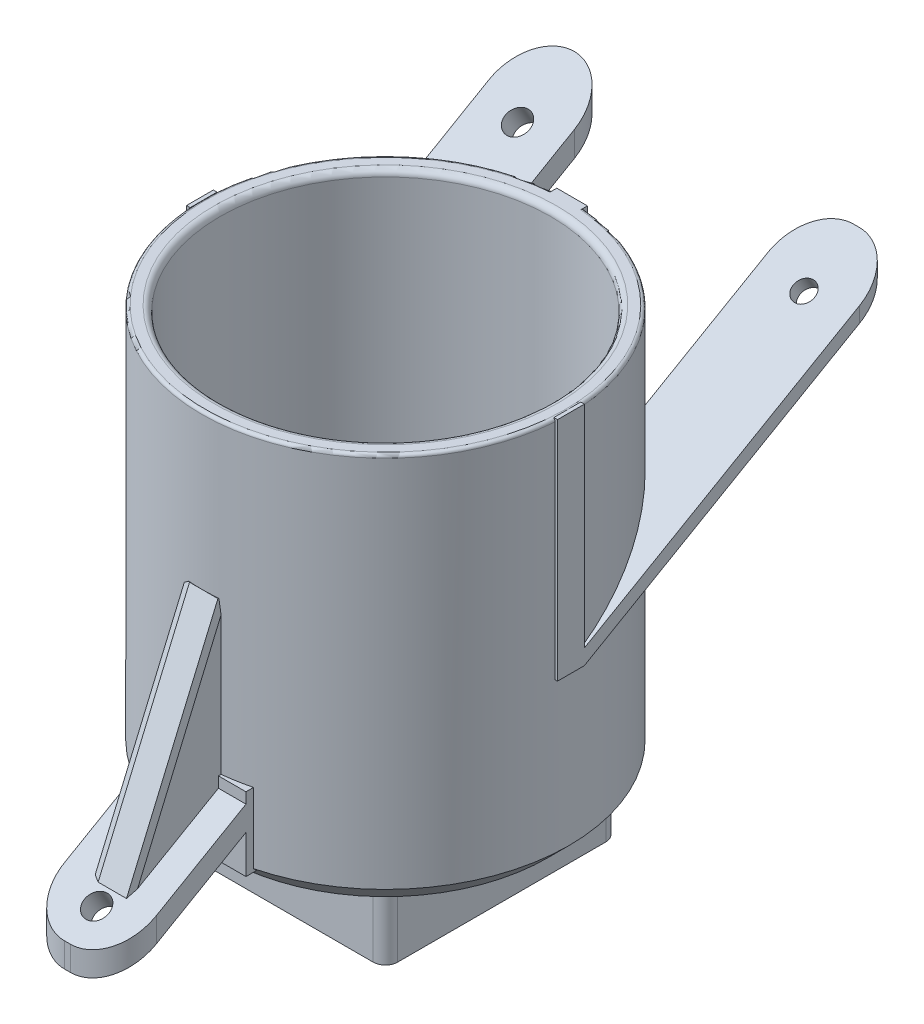
SolidWorks part; units mm, degrees
ref_plane "Alzado" through (0, 0, 0) normal (0, 0, 1) x (1, 0, 0)
ref_plane "Planta" through (0, 0, 0) normal (0, 1, 0) x (1, 0, 0)
ref_plane "Vista lateral" through (0, 0, 0) normal (1, 0, 0) x (0, 0, -1)
sketch "Croquis1" plane through (0, 0, 0) normal (0, 1, 0) x (1, 0, 0)
  circle A0 centre (0, 0) radius 16
  circle A1 centre (0, 0) radius 19
extrude "Saliente-Extruir1" add sketch "Croquis1" along normal blind 2.8
sketch "Croquis2" plane through (0, 0, 0) normal (0, -1, 0) x (-1, 0, 0)
  line L1 (16, 16) -> (-16, 16)
  line L2 (16, 16) -> (16, -16)
  line L3 (16, -16) -> (-16, -16)
  line L4 (-16, 16) -> (-16, -16)
  line L5 (16, 16) -> (-16, -16) construction
  line L6 (16, -16) -> (-16, 16) construction
  line L7 (19, 19) -> (-19, 19)
  line L8 (19, 19) -> (19, -19)
  line L9 (19, -19) -> (-19, -19)
  line L10 (-19, 19) -> (-19, -19)
  line L11 (19, 19) -> (-19, -19) construction
  line L12 (19, -19) -> (-19, 19) construction
  point P0 (0, 0)
  point P5 (0, 0)
extrude "Saliente-Extruir2" add sketch "Croquis2" along normal blind 10
sketch "Croquis3" plane through (0, 0, 0) normal (0, -1, 0) x (1, 0, 0)
  circle A1 centre (0, 0) radius 28
  circle A2 centre (0, 0) radius 16
extrude "Saliente-Extruir4" add sketch "Croquis3" against normal blind 3
sketch "Croquis4" plane through (0, 3, 0) normal (0, 1, 0) x (1, 0, 0)
  circle A2 centre (0, 0) radius 27
  circle A3 centre (0, 0) radius 30
extrude "Saliente-Extruir7" add sketch "Croquis4" along normal blind 63 and the other way up to surface other way up to face at (0, 0, -28)
chamfer "Chaflán2" distance 3.5 angle 45 1 edges at (0, 0, -30)
fillet "Redondeo5" radius 2 4 edges at (-19, -4.815, -19) (-19, -4.815, 19) (19, -4.815, 19) (19, -4.815, -19)
sketch "Croquis7" plane through (19, 0, 0) normal (1, 0, 0) x (0, 0, -1)
  line L1 (30, 66) -> (-30, 66) construction
  line L2 (0, 66) -> (0, 65)
  line L4 (-30, 65) -> (30, 65)
  line L5 (-30, 65) -> (-30, 66)
  line L6 (-30, 66) -> (30, 66)
  line L7 (30, 65) -> (30, 66)
  line L8 (-30, 65) -> (30, 66) construction
  line L9 (-30, 66) -> (30, 65) construction
  point P5 (0, 65.5)
extrude "Cortar-Extruir1" cut sketch "Croquis7" against normal through all and the other way through all contours L4 L7 L6 L2 | L6 L5 L4 L2
fillet "Redondeo6" radius 1 1 edges at (0, 65, -27)
fillet "Redondeo7" radius 0.5 1 edges at (0, 65, -30)
sketch "Croquis9" plane through (0, 65, 0) normal (0, 1, 0) x (1, 0, 0)
  line L0 (-2.5, 30) -> (-2.5, 30.5)
  line L3 (-2.5, 30) -> (-2.5, 29)
  line L4 (-2.5, 29) -> (0, 29)
  line L5 (0, 29) -> (2.5, 29)
  line L6 (2.5, 29) -> (2.5, 30)
  line L7 (-2.5, 30.5) -> (2.5, 30.5)
  line L8 (2.5, 30.5) -> (2.5, 30)
sketch "Croquis14" plane through (0, -10, 0) normal (0, -1, 0) x (1, 0, 0)
  line L5 (16.5, -16.5) -> (-16.5, -16.5)
  line L6 (16.5, -16.5) -> (16.5, 16.5)
  line L7 (16.5, 16.5) -> (-16.5, 16.5)
  line L8 (-16.5, -16.5) -> (-16.5, 16.5)
  line L9 (-16, 16) -> (16, 16)
  line L10 (-16, 16) -> (-16, -16)
  line L11 (-16, -16) -> (16, -16)
  line L12 (16, 16) -> (16, -16)
extrude "Cortar-Extruir2" cut sketch "Croquis14" against normal up to surface (10 mm away) up to face at (-11.7712, 0, 11.7712)
extrude "Saliente-Extruir8" add sketch "Croquis9" against normal blind 18
sketch "Croquis22" plane through (0, 65, 0) normal (0, 1, 0) x (1, 0, 0)
  line L1 (29.7, -2.194) -> (30.3, -2.194)
  line L2 (29.7, -2.194) -> (29.7, 2.194)
  line L3 (29.7, 2.194) -> (30.3, 2.194)
  line L4 (30.3, -2.194) -> (30.3, 2.194)
  line L5 (29.7, -2.194) -> (30.3, 2.194) construction
  line L6 (29.7, 2.194) -> (30.3, -2.194) construction
  line L7 (-30.3, -2.194) -> (-29.7, -2.194)
  line L8 (-30.3, -2.194) -> (-30.3, 2.194)
  line L9 (-30.3, 2.194) -> (-29.7, 2.194)
  line L10 (-29.7, -2.194) -> (-29.7, 2.194)
  line L11 (-30.3, -2.194) -> (-29.7, 2.194) construction
  line L12 (-30.3, 2.194) -> (-29.7, -2.194) construction
  arc A0 (-2.5, 29.8957) -> (2.5, 29.8957) centre (0, 0) ccw construction
  point P0 (30, 0)
  point P8 (-30, 0)
extrude "Saliente-Extruir9" add sketch "Croquis22" against normal blind 37
sketch "Croquis27" plane through (30.3, 0, 0) normal (1, 0, 0) x (0, 0, -1)
  line L0 (2.194, 28) -> (54.1555, 58)
  line L1 (2.194, 28) -> (2.194, 30.5)
  line L2 (2.194, 30.5) -> (54.1555, 60.5)
  line L3 (54.1555, 58) -> (54.1555, 60.5)
extrude "Saliente-Extruir10" add sketch "Croquis27" against normal blind 15
sketch "Croquis28" plane through (-30.3, 0, 0) normal (-1, 0, 0) x (0, 0, 1)
  line L0 (-2.194, 28) -> (-54.1555, 58)
  line L1 (-54.1555, 58) -> (-54.1555, 60.5)
  line L2 (-54.1555, 60.5) -> (-2.194, 30.5)
  line L3 (-2.194, 30.5) -> (-2.194, 28)
  line L4 (-2.194, 30.5) -> (-2.194, 32)
  line L5 (-2.194, 64.5) -> (-2.194, 28) construction
  line L6 (-2.194, 32) -> (-54.1555, 62.1174)
  line L7 (-54.1555, 62.1174) -> (-54.1555, 60.5)
  line M2 (-2.194, 65) -> (-2.194, 28)
sketch "Croquis31" plane through (0, 65, 0) normal (0, 1, 0) x (1, 0, 0)
  line L1 (-7.5, -30.2835) -> (7.5, -30.2835)
  line L2 (-7.5, -30.2835) -> (-7.5, -28.5835)
  line L3 (-7.5, -28.5835) -> (7.5, -28.5835)
  line L4 (7.5, -30.2835) -> (7.5, -28.5835)
  line L5 (-7.5, -30.2835) -> (7.5, -28.5835) construction
  line L6 (-7.5, -28.5835) -> (7.5, -30.2835) construction
  point P0 (0, -29.4335)
extrude "Saliente-Extruir13" add sketch "Croquis31" along normal blind 12 from offset 62 offset against normal yes
sketch "Croquis32" plane through (-7.5, 0, 0) normal (-1, 0, 0) x (0, 0, 1)
  line L2 (30.2835, 9.2491) -> (30.2835, 13.2491)
  line L3 (30.2835, 13.2491) -> (51.9341, 0.7491)
  line L4 (51.9341, 0.7491) -> (51.9341, -3.2509)
  line L5 (51.9341, -3.2509) -> (30.2835, 9.2491)
  point P2 (0, 0)
sketch "Croquis33" plane through (0, 0, -19) normal (0, 0, -1) x (-1, 0, 0)
  line L0 (0, 0) -> (0, -10)
  line L1 (0, -10) -> (0, -4.15)
  circle A0 centre (-8.8, -4.15) radius 0.25
  circle A1 centre (8.65, -4.15) radius 0.25
extrude "Cortar-Extruir3" cut sketch "Croquis33" against normal blind 0.3 contours A0 | A1
sketch "Croquis35" plane through (0, 3, 0) normal (0, 1, 0) x (1, 0, 0)
  circle A0 centre (0, 0) radius 27
sketch "Croquis36" plane through (0, 20.05, 11.5759) normal (0, -0.866, -0.5) x (1, 0, 0)
  circle A3 centre (0, 37.9414) radius 1.75
  circle A4 centre (-22.8, -67.2398) radius 1.75
  circle A5 centre (22.8, -67.2398) radius 1.75
extrude "Cortar-Extruir6" cut sketch "Croquis36" against normal blind 16.3
extrude "Saliente-Extruir14" add sketch "Croquis32" against normal up to surface (15 mm away) up to face at (7.5, 7.1293, 29.3434)
extrude "Saliente-Extruir15" add sketch "Croquis28" against normal blind 14 contours L2 L1 L0 M2 | L6 L7 L2 M2
sketch "Croquis37" plane through (0, 23.0011, 13.3317) normal (0, 0.8652, 0.5015) x (1, 0, 0)
  circle A0 centre (-23.3, 67.2826) radius 2
extrude "Cortar-Extruir7" cut sketch "Croquis37" against normal blind 14
ref_plane "Plano1" through (0, 20.05, 11.5759) normal (0, -0.866, -0.5) x (-1, 0, 0)
sketch "Croquis38" plane through (0, 20.05, 11.5759) normal (0, -0.866, -0.5) x (-1, 0, 0)
  circle A0 centre (0, -39.1017) radius 2
extrude "Cortar-Extruir8" cut sketch "Croquis38" against normal blind 14
fillet "Redondeo8" radius 7 6 edges at (15.3, 59.25, -54.1555) (30.3, 59.25, -54.1555) (-16.3, 60.0587, -54.1555) (-30.3, 60.0587, -54.1555) (7.5, -1.2509, 51.9341) (-7.5, -1.2509, 51.9341)
sketch3d "Croquis3D1" plane through (0, 0, 0) normal (0, 0, 1) x (1, 0, 0)
  dimension "D1" = 5
sketch "Croquis42" plane through (2.5, 0, 0) normal (1, 0, 0) x (0, 0, -1)
  line L0 (-44.9341, 4.7906) -> (-30, 39.75)
  line L1 (-30, 64.5) -> (-30, 15) construction
  line L3 (-30.2835, 15) -> (-29.0474, 15) construction
  line L4 (-30, 15) -> (-30.2835, 15)
  line L5 (-30.2835, 15) -> (-30.2835, 13.2491)
  line L6 (-30.2835, 13.2491) -> (-44.9341, 4.7906)
  line L7 (-30, 39.75) -> (-29, 39.75)
  line L8 (-29, 39.75) -> (-29.0474, 15)
  line L9 (-29.0474, 15) -> (-30.2835, 15)
extrude "Saliente-Extruir18" add sketch "Croquis42" against normal blind 5.5 and the other way blind 0.5 contours L9 L8 L7 L0 L6 L5 L4
chamfer "Chaflán3" distance 1 angle 20 2 edges at (-3, 22.2703, 37.467) (3, 22.2703, 37.467)
extrude "Cortar-Extruir9" cut sketch "Croquis35" along normal through all
